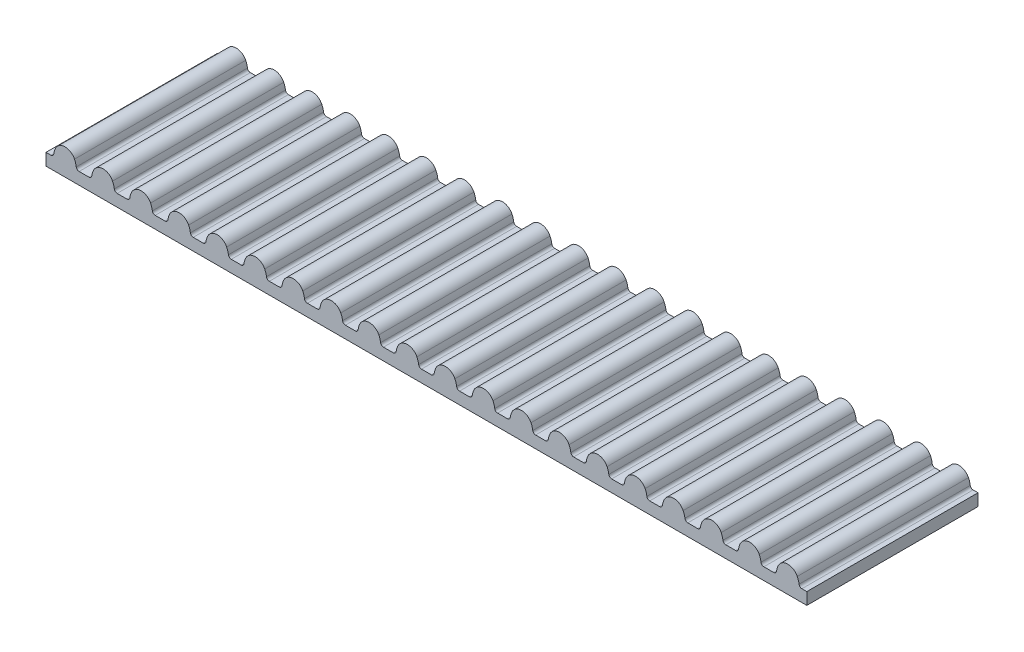
SolidWorks part; units mm, degrees
ref_plane "Front Plane" through (0, 0, 0) normal (0, 0, 1) x (1, 0, 0)
ref_plane "Top Plane" through (0, 0, 0) normal (0, 1, 0) x (1, 0, 0)
ref_plane "Right Plane" through (0, 0, 0) normal (1, 0, 0) x (0, 0, -1)
sketch "Width Sketch" plane through (0, 0, 0) normal (0, 0, 1) x (1, 0, 0)
  line L0 (0, 0) -> (1, 0)
  line L1 (1, 0) -> (1, 1.38)
  line L2 (1, 1.38) -> (1.4, 1.38) construction
  line L3 (1.4, 1.38) -> (1.4, 0.63) construction
  line L4 (1.4, 0.63) -> (0, 0.63) construction
  line L5 (0, 0.63) -> (0, 0)
  line L6 (0.2598, 0.63) -> (0, 0.63)
  arc A0 (1, 1.38) -> (0.5011, 1.0682) centre (1, 0.825) ccw
  arc A2 (0.5011, 1.0682) -> (0.4085, 0.7604) centre (1.4, 0.63) ccw
  arc A3 (0.4085, 0.7604) -> (0.2598, 0.63) centre (0.2598, 0.78) cw
  dimension "D5" = 0.4
  dimension "D4" = 0.555
  dimension "D6" = 1
  dimension "D7" = 0.15
  dimension "D1" = 1.38
  dimension "D2" = 0.75
  dimension "D3" = 1
extrude "Width Extrude" add sketch "Width Sketch" along normal blind 9
mirror "Mirror" about plane through (1, 0, 9) normal (-1, 0, 0) of bodies 101
pattern_linear "Pattern" count 20 spacing 2 along (1, 0, 0) of bodies 102
combine bodies "Combine" operation type add bodies to combine 102 121 120 119 118 117 116 115 114 113 112 111 110 109 108 107 106 105 104 103
